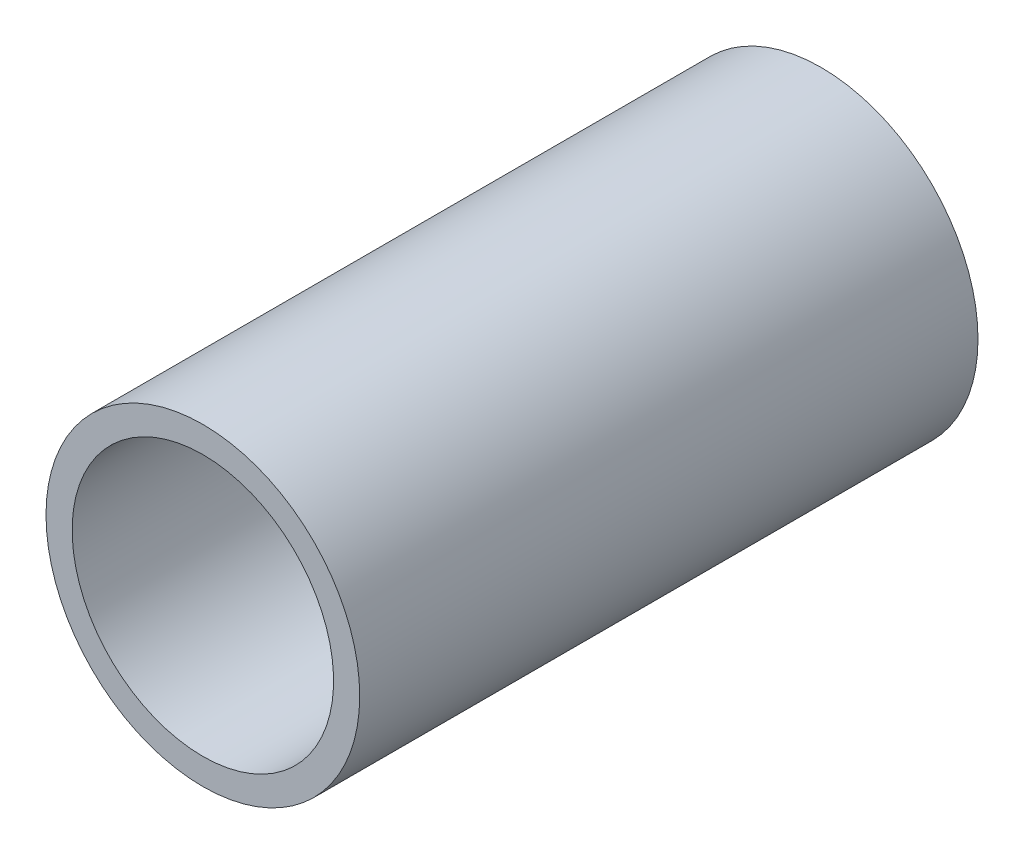
SolidWorks part; units mm, degrees
material "PLA 50%"
ref_plane "Front Plane" through (0, 0, 0) normal (0, 0, 1) x (1, 0, 0)
ref_plane "Top Plane" through (0, 0, 0) normal (0, 1, 0) x (1, 0, 0)
ref_plane "Right Plane" through (0, 0, 0) normal (1, 0, 0) x (0, 0, -1)
ref_axis "X" through (-88.99, 0, 0) along (1, 0, 0)
ref_axis "Y" through (0, 55, 0) along (0, -1, 0)
ref_axis "Z" through (0, 0, -88.99) along (0, 0, 1)
sketch "Sketch1" plane through (0, 0, 0) normal (0, 0, 1) x (1, 0, 0)
  circle A0 centre (0, 0) radius 5
  circle A1 centre (0, 0) radius 6
  dimension "D1" = 10
  dimension "D2" = 12
extrude "Boss-Extrude1" add sketch "Sketch1" along normal up to surface (23.65 mm away)
